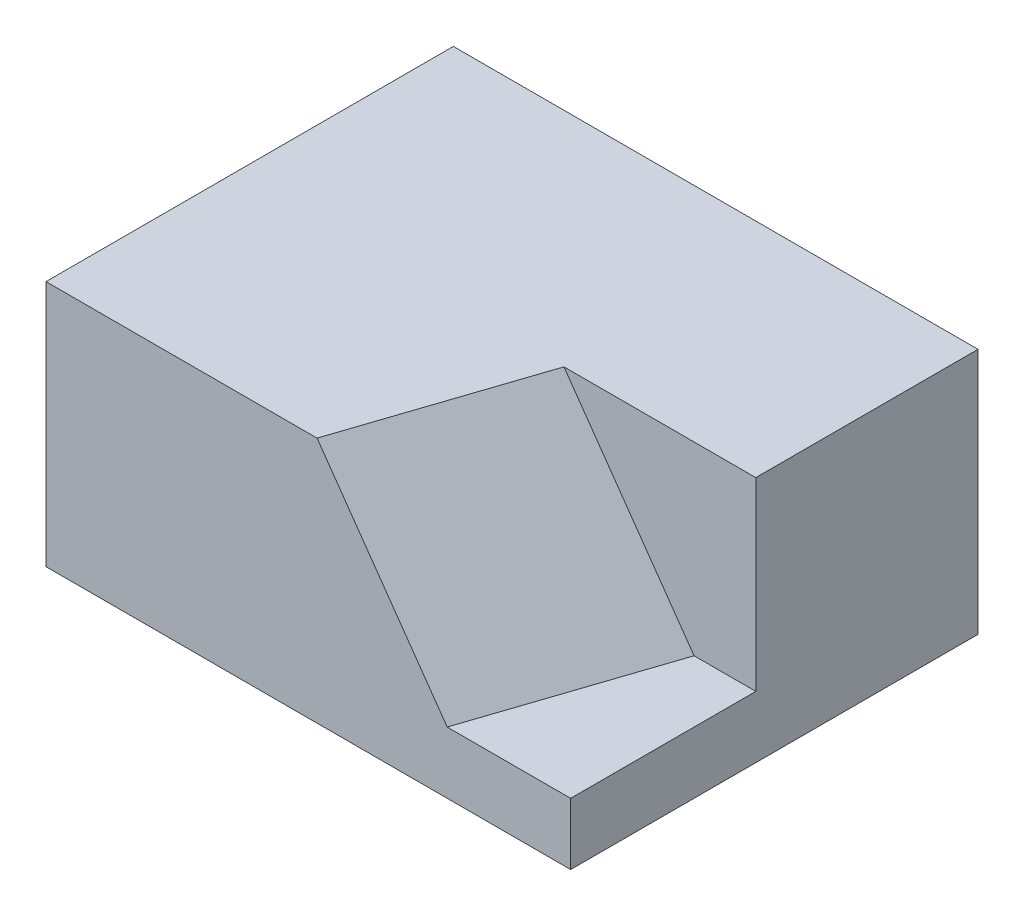
SolidWorks part; units mm, degrees
ref_plane "Front Plane" through (0, 0, 0) normal (0, 0, 1) x (1, 0, 0)
ref_plane "Top Plane" through (0, 0, 0) normal (0, 1, 0) x (1, 0, 0)
ref_plane "Right Plane" through (0, 0, 0) normal (1, 0, 0) x (0, 0, -1)
sketch "Sketch1" plane through (0, 0, 0) normal (0, 1, 0) x (1, 0, 0)
  line L1 (0, 0) -> (85, 0)
  line L2 (0, 0) -> (0, 66)
  line L3 (0, 66) -> (85, 66)
  line L4 (85, 0) -> (85, 66)
  dimension "D1" = 66
  dimension "D2" = 85
extrude "Boss-Extrude1" add sketch "Sketch1" along normal blind 40
sketch "Sketch3" plane through (0, 40, 0) normal (0, 1, 0) x (1, 0, 0)
  line L0 (85, 30) -> (75, 30)
  line L1 (85, 0) -> (85, 66) construction
  line L2 (75, 30) -> (65, 0)
  line L3 (0, 0) -> (85, 0) construction
  dimension "D1" = 10
  dimension "D2" = 30
  dimension "D3" = 20
extrude "Cut-Extrude1" cut sketch "Sketch3" against normal blind 30 and the other way through all
sketch "Sketch4" plane through (0, 40, 0) normal (0, 1, 0) x (1, 0, 0)
  line L0 (75, 30) -> (55, 30)
  line L1 (55, 30) -> (45, 0)
  line L2 (0, 0) -> (65, 0) construction
  dimension "D1" = 20
  dimension "D2" = 20
chamfer "Chamfer1" distance 30 distance2 20 1 edges at (70, 40, -15) first distance on face at (70, 25, -15)
